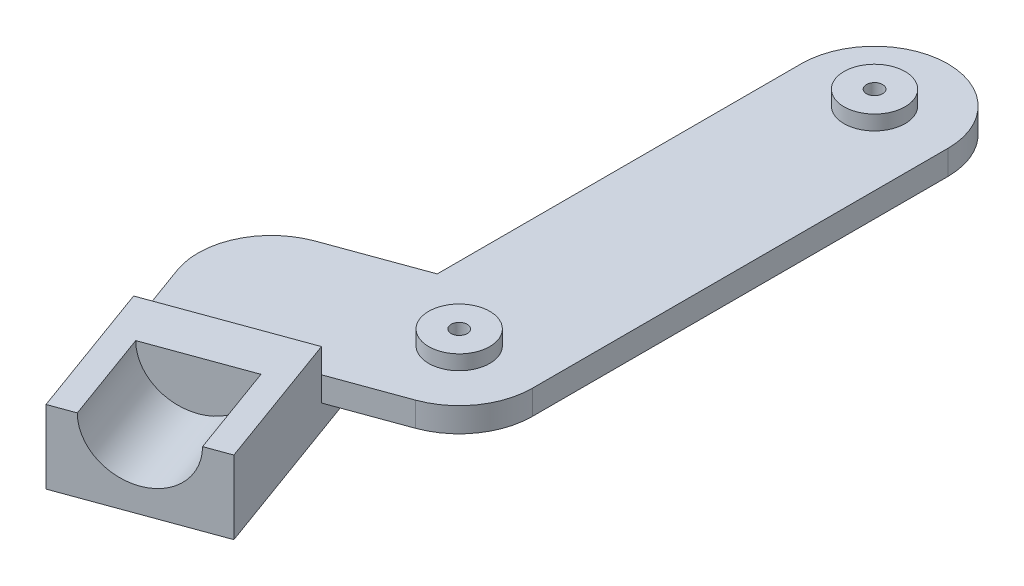
SolidWorks part; units mm, degrees
ref_plane "정면" through (0, 0, 0) normal (0, 0, 1) x (1, 0, 0)
ref_plane "윗면" through (0, 0, 0) normal (0, 1, 0) x (1, 0, 0)
ref_plane "우측면" through (0, 0, 0) normal (1, 0, 0) x (0, 0, -1)
sketch "스케치1" plane through (0, 0, 0) normal (0, 1, 0) x (1, 0, 0)
  line L0 (0, 0) -> (0, 85) construction
  line L2 (-15, 0) -> (-15, 85)
  line L3 (15, 0) -> (15, 85)
  arc A0 (-15, 0) -> (15, 0) centre (0, 0) ccw
  arc A1 (15, 85) -> (-15, 85) centre (0, 85) ccw
  point P5 (0, 42.5)
  dimension "D2" = 15
  dimension "D1" = 85
extrude "보스-돌출1" add sketch "스케치1" along normal blind 5
sketch "스케치2" plane through (0, 5, 0) normal (0, 1, 0) x (1, 0, 0)
  line L0 (0, 85) -> (0, 0) construction
  circle A0 centre (0, 85) radius 6.25
  circle A1 centre (0, 0) radius 6.25
  point P6 (0, 0)
  point P7 (0, 0)
  dimension "D2" = 12.5
  dimension "D3" = 12.5
  dimension "D1" = 85
extrude "보스-돌출2" add sketch "스케치2" along normal blind 3
hole_wizard "M4 탭을 위한 탭 드릴1" positions "스케치5" profile "스케치7" hole size "M4" standard "ISO"
sketch "스케치5" plane through (0, 8, 0) normal (0, 1, 0) x (1, 0, 0)
  point P0 (0, 0)
  point P3 (0, 85)
sketch "스케치7" plane through (0, 8, 0) normal (1, 0, 0) x (0, 0, 1)
  line L0 (0, 0) -> (0, 5.9914)
  line L1 (0, 5.9914) -> (1.65, 5)
  line L2 (1.65, 5) -> (1.65, 0)
  line L5 (1.65, 0) -> (0, 0)
  line L10 (0, 5.9914) -> (-1.65, 5) construction
  line L11 (0, -6.35) -> (0, 107.95) construction
  dimension "구멍 지름" = 3.3
  dimension "구멍 깊이" = 5
  dimension "드릴 각도" = 118
sketch "스케치9" plane through (0, 0, 0) normal (0, -1, 0) x (1, 0, 0)
  line L0 (0, 0) -> (-41.3824, 15.062) construction
  line L1 (-15, -85) -> (-15, 0) construction
  line L2 (0, 0) -> (-28.1908, 10.2606) construction
  line L3 (-5.1303, -14.0954) -> (-33.3211, -3.8348)
  line L4 (5.1303, 14.0954) -> (-23.0605, 24.356)
  arc A0 (-5.1303, -14.0954) -> (5.1303, 14.0954) centre (0, 0) ccw
  arc A1 (-23.0605, 24.356) -> (-33.3211, -3.8348) centre (-28.1908, 10.2606) ccw
  point P5 (-14.0954, 5.1303)
  dimension "D3" = 15
  dimension "D1" = 110
  dimension "D2" = 30
extrude "보스-돌출3" add sketch "스케치9" against normal blind 5
sketch "스케치10" plane through (0, 0, 0) normal (0, -1, 0) x (1, 0, 0)
  line L0 (-28.1908, 10.2606) -> (0, 0) construction
  line L3 (-42.2862, 15.3909) -> (-26.8953, 57.6771)
  line L6 (-28.1908, 10.2606) -> (-14.9216, 46.7173) construction
  line L7 (-14.0954, 5.1303) -> (1.2955, 47.4165)
  line L8 (-26.8953, 57.6771) -> (1.2955, 47.4165)
  arc A4 (-42.2862, 15.3909) -> (-14.0954, 5.1303) centre (-28.1908, 10.2606) ccw
  dimension "D2" = 90
  dimension "D3" = 45
  dimension "D1" = 30
extrude "보스-돌출4" add sketch "스케치10" against normal blind 5 and the other way blind 5
sketch "스케치11" plane through (0, 5, 0) normal (0, 1, 0) x (1, 0, 0)
  line L0 (-26.8953, -57.6771) -> (-42.2862, -15.3909) construction
  line L1 (1.2955, -47.4165) -> (-26.8953, -57.6771) construction
  line L2 (-8.9651, -19.2257) -> (1.2955, -47.4165) construction
  line L3 (-26.8953, -57.6771) -> (-37.1559, -29.4863)
  line L4 (1.2955, -47.4165) -> (-26.8953, -57.6771)
  line L5 (-8.9651, -19.2257) -> (1.2955, -47.4165)
  line L6 (-8.9651, -19.2257) -> (-37.1559, -29.4863)
extrude "보스-돌출5" add sketch "스케치11" along normal blind 5
sketch "스케치12" plane through (15.3909, 0, 42.2862) normal (0.342, 0, 0.9397) x (0.9397, 0, -0.342)
  line L0 (-45, 10) -> (-15, 10) construction
  circle A0 centre (-30, 10) radius 10
  dimension "D1" = 20
extrude "컷-돌출1" cut sketch "스케치12" against normal blind 20
